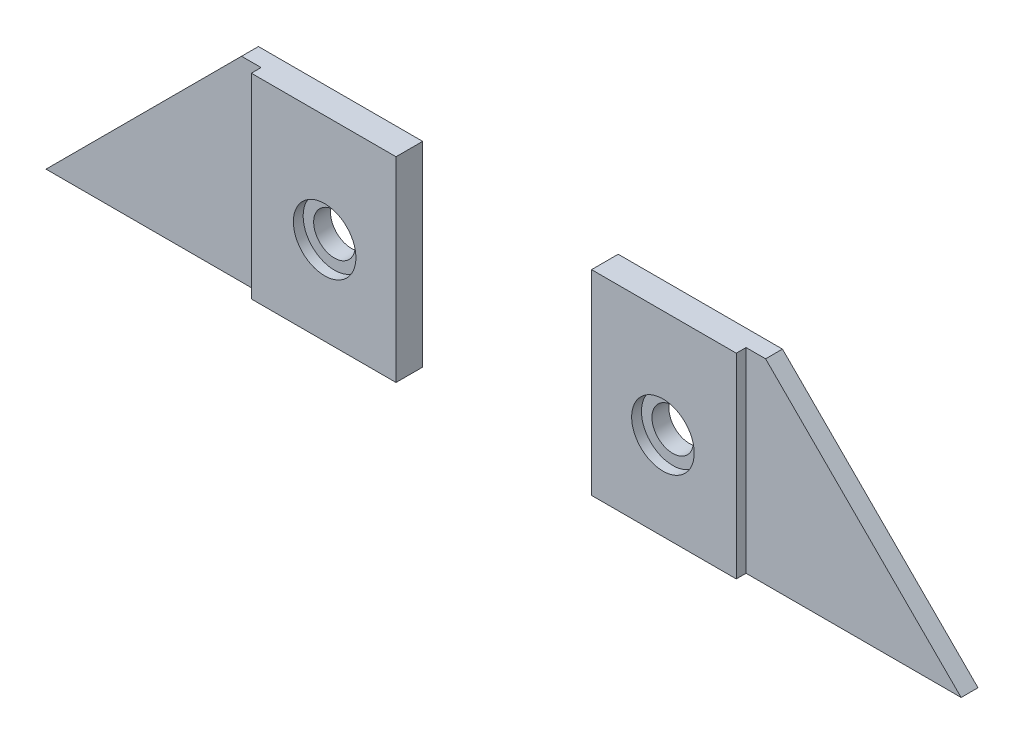
SolidWorks part; units mm, degrees
ref_plane "Front Plane" through (0, 0, 0) normal (0, 0, 1) x (1, 0, 0)
ref_plane "Top Plane" through (0, 0, 0) normal (0, 1, 0) x (1, 0, 0)
ref_plane "Right Plane" through (0, 0, 0) normal (1, 0, 0) x (0, 0, -1)
sketch "Sketch1" plane through (0, 0, 0) normal (0, 1, 0) x (1, 0, 0)
  line L0 (-18.4, -1.3625) -> (18.4, 1.3625) construction
  line L1 (-18.4, 1.3625) -> (18.4, 1.3625)
  line L2 (-18.4, 1.3625) -> (-18.4, -1.3625)
  line L3 (-18.4, -1.3625) -> (-3.6, -1.3625)
  line L4 (-3.6, -0.3625) -> (-3.6, -1.3625)
  line L7 (-3.6, -0.3625) -> (18.4, -0.3625)
  line L8 (18.4, 1.3625) -> (18.4, -0.3625)
  dimension "D1" = 14.8
  dimension "D2" = 2.725
  dimension "D3" = 1
  dimension "D4" = 22
  dimension "D5" = 1.725
extrude "Boss-Extrude1" add sketch "Sketch1" along normal blind 10 and the other way blind 10
sketch "Sketch2" plane through (0, 0, 0.3625) normal (0, 0, 1) x (1, 0, 0)
  line L0 (-1.6, 10) -> (18.4, -10)
  line L1 (-3.6, 10) -> (18.4, 10) construction
  line L2 (18.4, -10) -> (18.4, 10) construction
  line L3 (18.4, -10) -> (18.4, 10)
  line L4 (18.4, 10) -> (-1.6, 10)
  dimension "D1" = 20
  dimension "D2" = 20
extrude "Cut-Extrude1" cut sketch "Sketch2" against normal blind 2
sketch "Sketch3" plane through (0, 0, 1.3625) normal (0, 0, 1) x (1, 0, 0)
  line L1 (-3.6, -10) -> (-18.6, -10) construction
  line L2 (-18.6, -10) -> (-11.1, -1) construction
  line L3 (-11.1, -1) -> (-3.6, -10) construction
  circle A0 centre (-11.1, -1) radius 2.125
  point P3 (-11.1, 0)
  dimension "D1" = 4.25
  dimension "D2" = 15
  dimension "D3" = 9
extrude "Cut-Extrude2" cut sketch "Sketch3" against normal blind 3
sketch "Sketch4" plane through (0, 0, 1.3625) normal (0, 0, 1) x (1, 0, 0)
  circle A0 centre (-11.1, -1) radius 3.2
  dimension "D1" = 6.4
extrude "Cut-Extrude3" cut sketch "Sketch4" against normal blind 1
ref_plane "Plane1" through (-28.4, 0, 0) normal (-1, 0, 0) x (0, 0, 1)
mirror "Mirror1" about plane through (-28.4, 0, 0) normal (-1, 0, 0) of bodies 104
